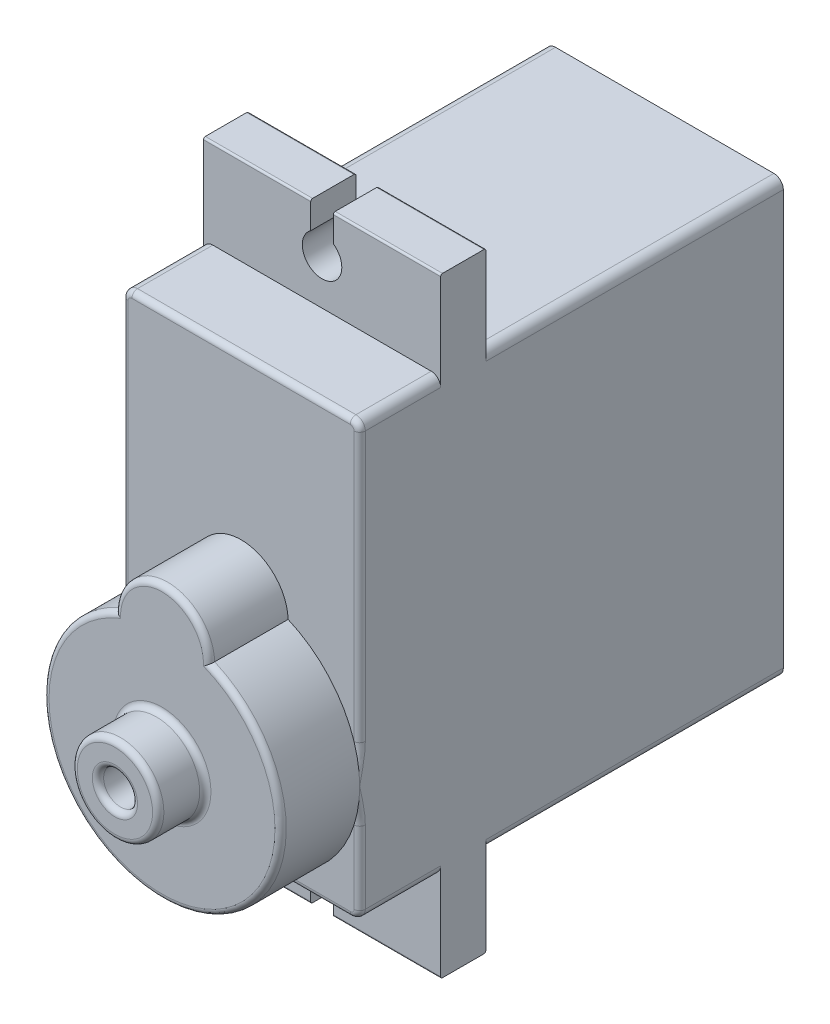
SolidWorks part; units mm, degrees
ref_plane "正面" through (0, 0, 0) normal (0, 0, 1) x (1, 0, 0)
ref_plane "平面" through (0, 0, 0) normal (0, 1, 0) x (1, 0, 0)
ref_plane "右側面" through (0, 0, 0) normal (1, 0, 0) x (0, 0, -1)
sketch "ｽｹｯﾁ1" plane through (0, 0, 0) normal (0, 0, 1) x (1, 0, 0)
  line L0 (-6.3, 11.5) -> (6.3, 11.5)
  line L1 (-6.3, -16.2) -> (6.3, -16.2)
  line L2 (-6.3, -16.2) -> (-6.3, 16.2)
  line L3 (-6.3, 16.2) -> (6.3, 16.2)
  line L4 (6.3, -16.2) -> (6.3, 16.2)
  line L5 (-6.3, -16.2) -> (6.3, 16.2) construction
  line L6 (-6.3, 16.2) -> (6.3, -16.2) construction
  line L7 (6.3, -11.5) -> (-6.3, -11.5)
  line L8 (0, -16.2) -> (0, 16.2) construction
  line L9 (-6.3, 13.9) -> (6.3, 13.9) construction
  line L10 (-0.6, 13.9) -> (-0.6, 16.2)
  line L11 (0.6, 13.9) -> (0.6, 16.2)
  line L12 (-6.3, 0) -> (6.3, 0) construction
  line L13 (-0.6, -13.9) -> (-0.6, -16.2)
  line L14 (0.6, -13.9) -> (0.6, -16.2)
  circle A0 centre (0, 13.9) radius 1.05
  circle A1 centre (0, -13.9) radius 1.05
  point P0 (0, 0)
  dimension "D3" = 2.1
  dimension "D1" = 0.6
  dimension "D2" = 0.6
  dimension "D4" = 13.9
  dimension "D5" = 32.4
  dimension "D6" = 11.5
  dimension "D7" = 11.5
  dimension "D8" = 12.6
extrude "ﾎﾞｽ - 押し出し1" add sketch "ｽｹｯﾁ1" along normal blind 22.5 contours L7 L4 L0 L2 region at (0, 0, 0)
extrude "ﾎﾞｽ - 押し出し2" add sketch "ｽｹｯﾁ1<4>" along normal blind 2.4 from offset 15.8 contours A0 L10 L3 L2 L0 L4 L11 | L13 A1 L14 L1 L4 L7 L2 region at (-6.1655, 13.85, 0) region at (0, -11.6345, 0)
sketch "ｽｹｯﾁ1<4>" plane through (0, 0, 0) normal (0, 0, 1) x (1, 0, 0) same geometry as "ｽｹｯﾁ1"
fillet "ﾌｨﾚｯﾄ1" radius 0.5 8 edges at (6.3, 11.5, 7.9) (6.3, 11.5, 20.35) (6.3, -11.5, 7.9) (6.3, -11.5, 20.35) (-6.3, 11.5, 7.9) (-6.3, 11.5, 20.35) (-6.3, -11.5, 7.9) (-6.3, -11.5, 20.35)
ref_plane "Layer_01" through (0, 0, 22.5) normal (0, 0, 1) x (1, 0, 0)
sketch "ｽｹｯﾁ2" plane through (0, 0, 22.5) normal (0, 0, 1) x (1, 0, 0)
  line L0 (-5.8, 11.5) -> (5.8, 11.5) construction
  line L1 (-6.3, -11.5) -> (6.3, -11.5) construction
  line L2 (-6.3, -11.5) -> (-6.3, 11.5) construction
  line L3 (-6.3, 11.5) -> (6.3, 11.5) construction
  line L4 (6.3, -11.5) -> (6.3, 11.5) construction
  line L5 (-6.3, -11.5) -> (6.3, 11.5) construction
  line L6 (-6.3, 11.5) -> (6.3, -11.5) construction
  line L7 (-6.3, -11) -> (-6.3, 11) construction
  line L8 (6.3, -11) -> (6.3, 11) construction
  line L9 (5.8, -11.5) -> (-5.8, -11.5) construction
  line L10 (0, 0) -> (0, -11.5) construction
  line L11 (0, -11.5) -> (0, 3) construction
  circle A0 centre (0, -5.2) radius 6.3
  circle A1 centre (0, -5.2) radius 2.3
  circle A2 centre (0, -5.2) radius 0.9
  circle A3 centre (0, 0.5) radius 2.5
  point P4 (0, 0)
  dimension "D1" = 6.3
  dimension "D2" = 4.6
  dimension "D3" = 1.8
  dimension "D5" = 5
  dimension "D4" = 14.5
extrude "ﾎﾞｽ - 押し出し4" add sketch "ｽｹｯﾁ2" along normal blind 4.2 contours A0 A3 | A0 A3 | A3 A0 A1 region at (-3.3645, -10.3187, 22.5) region at (0, -0.3266, 22.5) region at (0, 1.7909, 22.5)
extrude "ﾎﾞｽ - 押し出し5" add sketch "ｽｹｯﾁ2<4>" along normal blind 6.7 contours A1 A2 region at (-2.2349, -5.2, 22.5)
sketch "ｽｹｯﾁ2<4>" plane through (0, 0, 22.5) normal (0, 0, 1) x (1, 0, 0) same geometry as "ｽｹｯﾁ2"
fillet "ﾌｨﾚｯﾄ2" radius 0.1 8 edges at (-3.45, 16.2, 18.2) (-3.45, 16.2, 15.8) (3.45, 16.2, 15.8) (3.45, 16.2, 18.2) (-3.45, -16.2, 15.8) (3.45, -16.2, 15.8) (3.45, -16.2, 18.2) (-3.45, -16.2, 18.2)
fillet "ﾌｨﾚｯﾄ4" radius 0.3 1 edges at (2.3, -5.2, 29.2)
fillet "ﾌｨﾚｯﾄ5" radius 0.3 1 edges at (0.9, -5.2, 29.2)
fillet "ﾌｨﾚｯﾄ6" radius 0.3 11 edges at (6.3, 2.9, 22.5) (6.1536, 11.3536, 22.5) (6.1536, -11.3536, 22.5) (6.3, -8.1, 22.5) (2.9, -11.5, 22.5) (-2.9, -11.5, 22.5) (-6.1536, -11.3536, 22.5) (-6.3, -8.1, 22.5) (0, 11.5, 22.5) (-6.1536, 11.3536, 22.5) (-6.3, 2.9, 22.5)
fillet "ﾌｨﾚｯﾄ8" radius 0.3 3 edges at (2.3, -5.2, 26.7) (0, -11.5, 26.7) (0, 3, 26.7)
